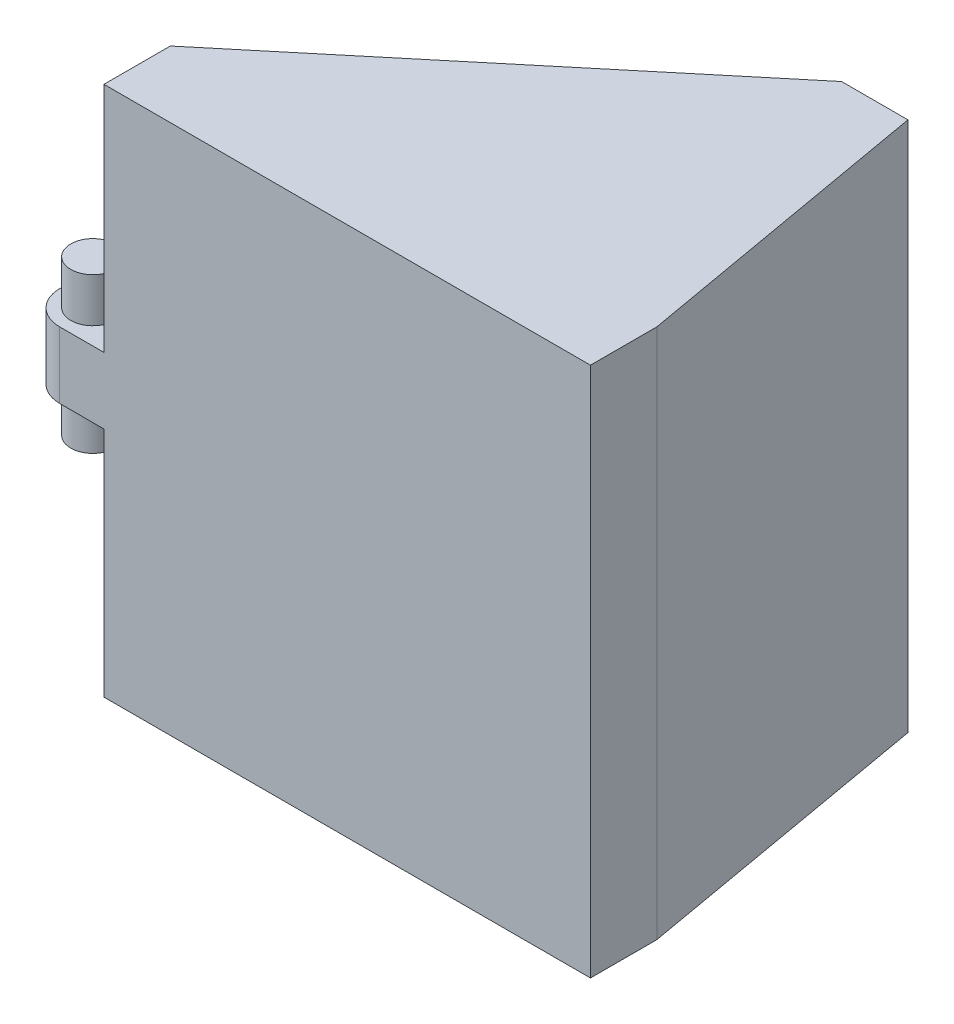
SolidWorks part; units mm, degrees
ref_plane "前视基准面" through (0, 0, 0) normal (0, 0, 1) x (1, 0, 0)
ref_plane "上视基准面" through (0, 0, 0) normal (0, 1, 0) x (1, 0, 0)
ref_plane "右视基准面" through (0, 0, 0) normal (1, 0, 0) x (0, 0, -1)
sketch "草图1" plane through (0, 0, 0) normal (0, 1, 0) x (1, 0, 0)
  line L0 (0, 0) -> (120, 0)
  line L1 (0, 15) -> (120, 15)
  line L7 (120, 15) -> (120, 0)
  arc A1 (0, 0) -> (0, 15) centre (0, 7.5) cw
  circle A3 centre (0, 7.5) radius 5
extrude "凸台-拉伸1" add sketch "草图1" along normal blind 7.5 and the other way blind 7.5
ref_plane "基准面4" through (0, 17.5, 0) normal (0, 1, 0) x (1, 0, 0)
sketch "草图2" plane through (0, 0, 0) normal (0, 1, 0) x (1, 0, 0)
  circle A0 centre (0, 7.5) radius 5
extrude "凸台-拉伸2" add sketch "草图2" against normal mid plane 35
sketch "草图3" plane through (0, 0, 0) normal (0, 1, 0) x (1, 0, 0)
  line L1 (10, 0) -> (120, 0)
  line L2 (10, 0) -> (10, 15)
  line L3 (10, 15) -> (120, 15)
  line L4 (120, 0) -> (120, 15)
extrude "凸台-拉伸3" add sketch "草图3" along normal mid plane 120
sketch "草图4" plane through (0, 60, 0) normal (0, 1, 0) x (1, 0, 0)
  line L0 (120, 15) -> (105, 15)
  line L1 (120, 15) -> (10, 15) construction
  line L2 (105, 15) -> (92.8446, 83.9365)
  line L3 (92.8446, 83.9365) -> (107.8446, 83.9365)
  line L4 (107.8446, 83.9365) -> (120, 15)
extrude "凸台-拉伸4" add sketch "草图4" against normal up to surface (120 mm away) up to face at (65, -60, -7.5)
sketch "草图5" plane through (0, 60, 0) normal (0, 1, 0) x (1, 0, 0)
  line L0 (10, 15) -> (92.8446, 83.9365)
  line L1 (92.8446, 83.9365) -> (105, 15)
  line L2 (105, 15) -> (10, 15)
  point P6 (105, 65)
  point P7 (103.8176, 64.2404)
  point P8 (96.3176, 64.2404)
extrude "凸台-拉伸5" add sketch "草图5" against normal blind 5
sketch "草图6" plane through (0, -60, 0) normal (0, -1, 0) x (1, 0, 0)
  line L0 (10, -15) -> (92.8446, -83.9365)
  line L2 (105, -15) -> (10, -15) construction
  line L3 (92.8446, -83.9365) -> (105, -15) construction
  line L4 (105, -15) -> (10, -15)
  line L5 (92.8446, -83.9365) -> (105, -15)
extrude "凸台-拉伸6" add sketch "草图6" against normal blind 5
chamfer "倒角1" distance 15 angle 85 1 edges at (92.8446, 0, -83.9365) first distance on face at (97.8446, 0, -83.9365)
fillet "圆角1" radius 10 1 edges at (105, 0, -15)
